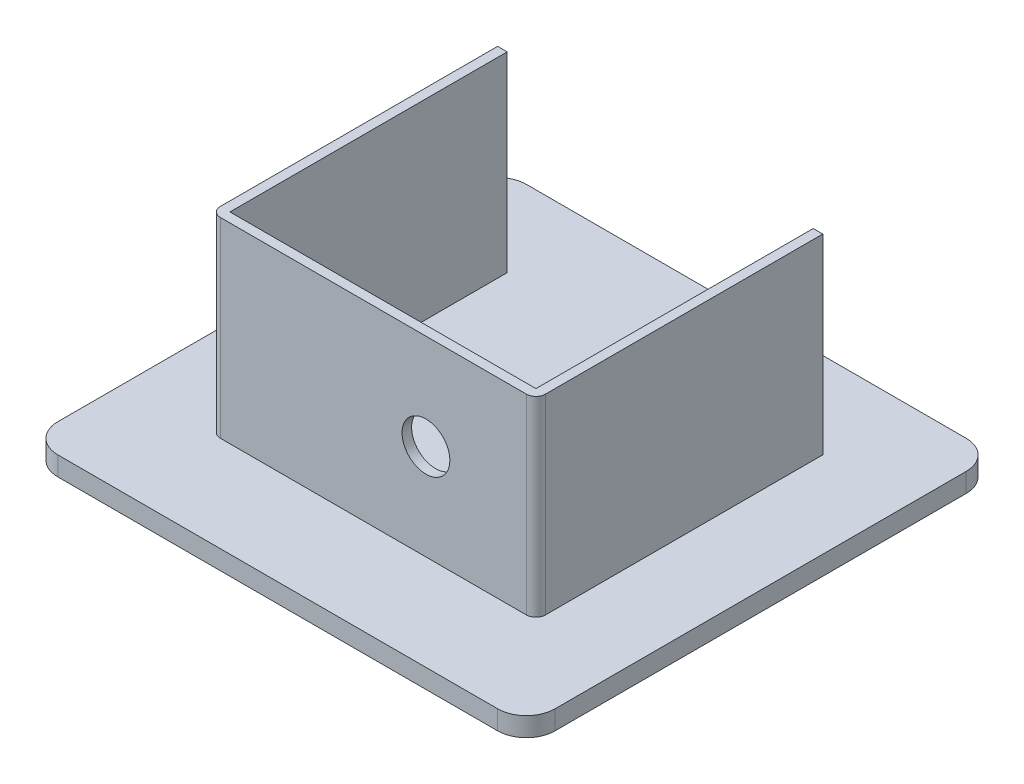
SolidWorks part; units mm, degrees
ref_plane "Front Plane" through (0, 0, 0) normal (0, 0, 1) x (1, 0, 0)
ref_plane "Top Plane" through (0, 0, 0) normal (0, 1, 0) x (1, 0, 0)
ref_plane "Right Plane" through (0, 0, 0) normal (1, 0, 0) x (0, 0, -1)
other "Configuration Table"
sketch "Sketch3" plane through (0, 0, 0) normal (0, 1, 0) x (1, 0, 0)
  line L0 (-91.0159, 50.8359) -> (-91.0159, 1.8359)
  line L1 (-91.0159, 50.8359) -> (-39.0159, 50.8359)
  line L3 (-91.0159, 1.8359) -> (-39.0159, 1.8359)
  line L5 (-39.0159, 50.8359) -> (-39.0159, 1.8359)
  dimension "D1" = 52
  dimension "D2" = 49
extrude "Boss-Extrude3" add sketch "Sketch3" along normal blind 2
sketch "Sketch5" plane through (0, 0, 0) normal (0, -1, 0) x (1, 0, 0)
  line L0 (-91.0159, -50.8359) -> (-91.0159, -1.8359) construction
  circle A0 centre (-62.0159, -26.3359) radius 3.5
  circle A1 centre (-62.0159, -26.3359) radius 2.5
  dimension "D1" = 5
  dimension "D2" = 7
  dimension "D3" = 29
extrude "Boss-Extrude5" add sketch "Sketch5" along normal blind 3
fillet "Fillet1" radius 3 4 edges at (-91.0159, 1, -50.8359) (-91.0159, 1, -1.8359) (-39.0159, 1, -50.8359) (-39.0159, 1, -1.8359)
sketch "Sketch11" plane through (0, 2, 0) normal (0, 1, 0) x (1, 0, 0)
  line L0 (-91.0159, 47.8359) -> (-91.0159, 4.8359) construction
  line L2 (-81.0159, 39.8359) -> (-81.0159, 12.8359)
  line L3 (-81.0159, 12.8359) -> (-49.0159, 12.8359)
  line L4 (-49.0159, 39.8359) -> (-49.0159, 12.8359)
  line L5 (-88.0159, 1.8359) -> (-42.0159, 1.8359) construction
  line L7 (-81.0159, 39.8359) -> (-81.0159, 41.8359)
  line L8 (-82.0159, 41.8359) -> (-81.0159, 41.8359)
  line L9 (-82.0159, 41.8359) -> (-82.0159, 11.8359)
  line L10 (-82.0159, 11.8359) -> (-48.0159, 11.8359)
  line L11 (-48.0159, 41.8359) -> (-48.0159, 11.8359)
  line L12 (-49.0159, 39.8359) -> (-49.0159, 41.8359)
  line L13 (-49.0159, 41.8359) -> (-48.0159, 41.8359)
  dimension "D1" = 27
  dimension "D2" = 32
  dimension "D3" = 10
  dimension "D4" = 11
  dimension "D6" = 1
  dimension "D7" = 1
  dimension "D8" = 1
extrude "Boss-Extrude11" add sketch "Sketch11" along normal blind 20
sketch "Sketch12" plane through (0, 0, -11.8359) normal (0, 0, 1) x (1, 0, 0)
  line L0 (-48.0159, 22) -> (-48.0159, 2) construction
  circle A0 centre (-59.5159, 12) radius 2.5
  dimension "D1" = 5
  dimension "D2" = 11.5
extrude "Cut-Extrude2" cut sketch "Sketch12" against normal through all
fillet "Fillet5" radius 1 2 edges at (-82.0159, 12, -11.8359) (-48.0159, 12, -11.8359)
